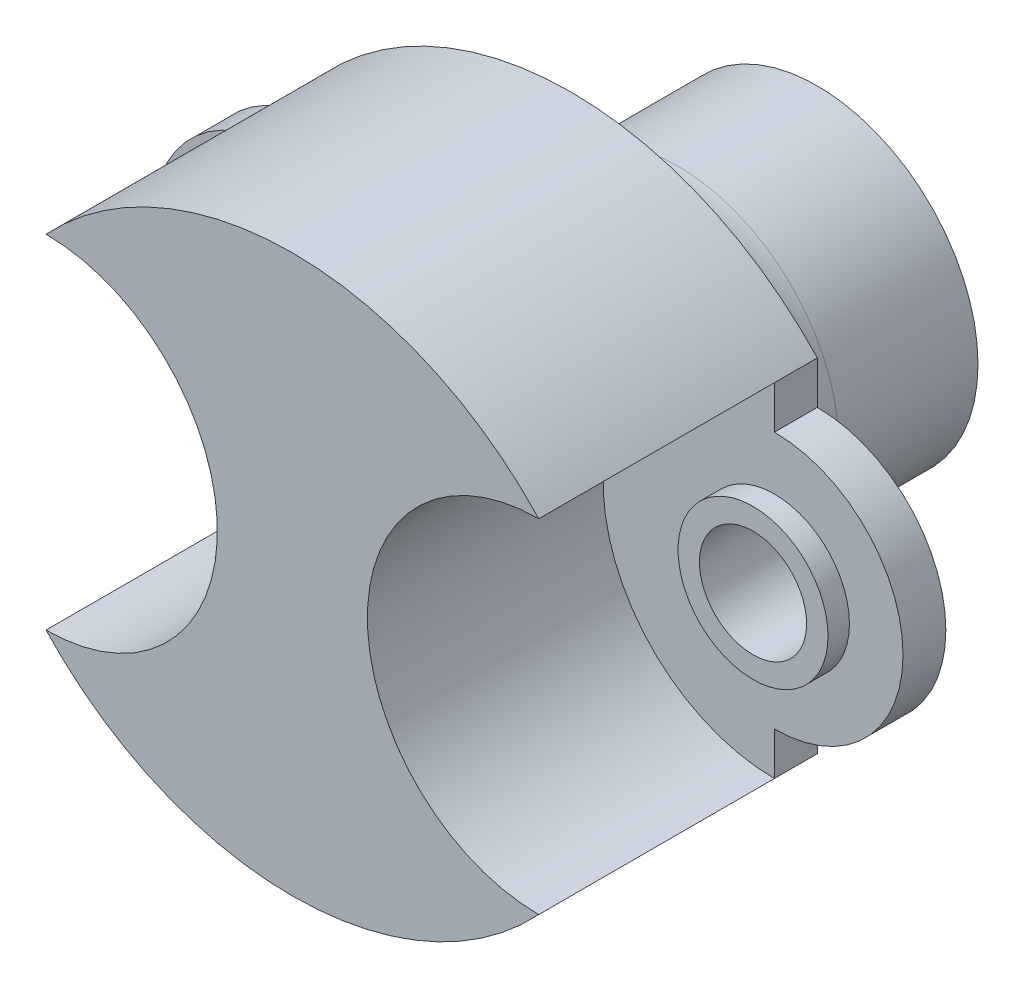
SolidWorks part; units mm, degrees
ref_plane "Płaszczyzna przednia" through (0, 0, 0) normal (0, 0, 1) x (1, 0, 0)
ref_plane "Płaszczyzna górna" through (0, 0, 0) normal (0, 1, 0) x (1, 0, 0)
ref_plane "Płaszczyzna prawa" through (0, 0, 0) normal (1, 0, 0) x (0, 0, -1)
sketch "Szkic1" plane through (0, 0, 0) normal (0, 0, 1) x (1, 0, 0)
  arc A7 (11.5, -8) -> (11.5, 8) centre (11.5, 0) ccw
  arc A8 (-11.5, 8) -> (-11.5, -8) centre (-11.5, 0) ccw
  arc A9 (-11.5, 8) -> (11.5, 8) centre (0, -2.725) cw
  arc A10 (-11.5, -8) -> (11.5, -8) centre (0, 2.725) ccw
  point P14 (0, 13)
  point P15 (0, -13)
  dimension "D3" = 8
  dimension "D7" = 8
  dimension "D9" = 13
  dimension "D2" = 11.5
  dimension "D4" = 11.5
  dimension "D5" = 0
  dimension "D6" = 0
  dimension "D10" = 13
extrude "Dodanie-wyciągnięcie1" add sketch "Szkic1" along normal blind 3
sketch "Szkic2" plane through (0, 0, 3) normal (0, 0, 1) x (1, 0, 0)
  circle A0 centre (11.5, 0) radius 2.45
  circle A1 centre (-11.5, 0) radius 2.45
  dimension "D1" = 4.9
  dimension "D2" = 4.9
extrude "Dodanie-wyciągnięcie2" add sketch "Szkic2" along normal blind 9
sketch "Szkic3" plane through (0, 0, 12) normal (0, 0, 1) x (1, 0, 0)
  circle A0 centre (11.5, 0) radius 2.5
  circle A1 centre (-11.5, 0) radius 2.5
  dimension "D1" = 5
  dimension "D2" = 5
extrude "Wytnij-wyciągnięcie1" cut sketch "Szkic3" against normal up to next
sketch "Szkic4" plane through (0, 0, 3) normal (0, 0, 1) x (1, 0, 0)
  arc A0 (-11.5, -8) -> (-11.5, 8) centre (-11.5, 0) ccw
  arc A1 (11.5, 8) -> (11.5, -8) centre (11.5, 0) ccw
  arc A4 (-11.5, 8) -> (11.5, 8) centre (0, -2.725) cw
  arc A5 (-11.5, -8) -> (11.5, -8) centre (0, 2.725) ccw
  dimension "D1" = 15.725
  dimension "D2" = 15.725
extrude "Dodanie-wyciągnięcie3" add sketch "Szkic4" along normal blind 10
sketch "Szkic5" plane through (0, 0, 0) normal (0, 0, -1) x (-1, 0, 0)
  circle A0 centre (0, 0) radius 7.5
  dimension "D1" = 15
extrude "Dodanie-wyciągnięcie4" add sketch "Szkic5" along normal blind 11.5
fillet "Zaokrąglenie1" radius 5 1 edges at (-7.5, 0, 0)
sketch "Szkic6" plane through (0, 0, -11.5) normal (0, 0, -1) x (-1, 0, 0)
  line L1 (-2.55, -2.55) -> (2.55, -2.55)
  line L2 (-2.55, -2.55) -> (-2.55, 2.55)
  line L3 (-2.55, 2.55) -> (2.55, 2.55)
  line L4 (2.55, -2.55) -> (2.55, 2.55)
  line L5 (-2.55, -2.55) -> (2.55, 2.55) construction
  line L6 (-2.55, 2.55) -> (2.55, -2.55) construction
  point P0 (0, 0)
  dimension "D1" = 5.1
  dimension "D2" = 5.1
extrude "Wytnij-wyciągnięcie2" cut sketch "Szkic6" against normal blind 7
sketch "Szkic8" plane through (0, 0, 3) normal (0, 0, 1) x (1, 0, 0)
  circle A0 centre (-11.5, 0) radius 3.5
  circle A1 centre (-11.5, 0) radius 8
  circle A2 centre (11.5, 0) radius 3.5
  circle A3 centre (11.5, 0) radius 8
  dimension "D1" = 7
  dimension "D2" = 7
  dimension "D3" = 16
  dimension "D4" = 16
extrude "Wytnij-wyciągnięcie3" cut sketch "Szkic8" against normal blind 1
sketch "Szkic9" plane through (0, 0, 2) normal (0, 0, 1) x (1, 0, 0)
  line L0 (11.5, 8) -> (11.5, 6)
  line L1 (11.5, -6) -> (11.5, -8)
  line L2 (-11.5, 8) -> (-11.5, 6)
  line L3 (-11.5, -6) -> (-11.5, -8)
  arc A0 (11.5, -6) -> (11.5, 6) centre (11.5, 0) ccw
  arc A1 (11.5, -8) -> (11.5, 8) centre (11.5, 0) ccw
  arc A2 (-11.5, 6) -> (-11.5, -6) centre (-11.5, 0) ccw
  arc A3 (-11.5, 8) -> (-11.5, -8) centre (-11.5, 0) ccw
  dimension "D1" = 12
  dimension "D3" = 12
extrude "Wytnij-wyciągnięcie4" cut sketch "Szkic9" against normal up to next
